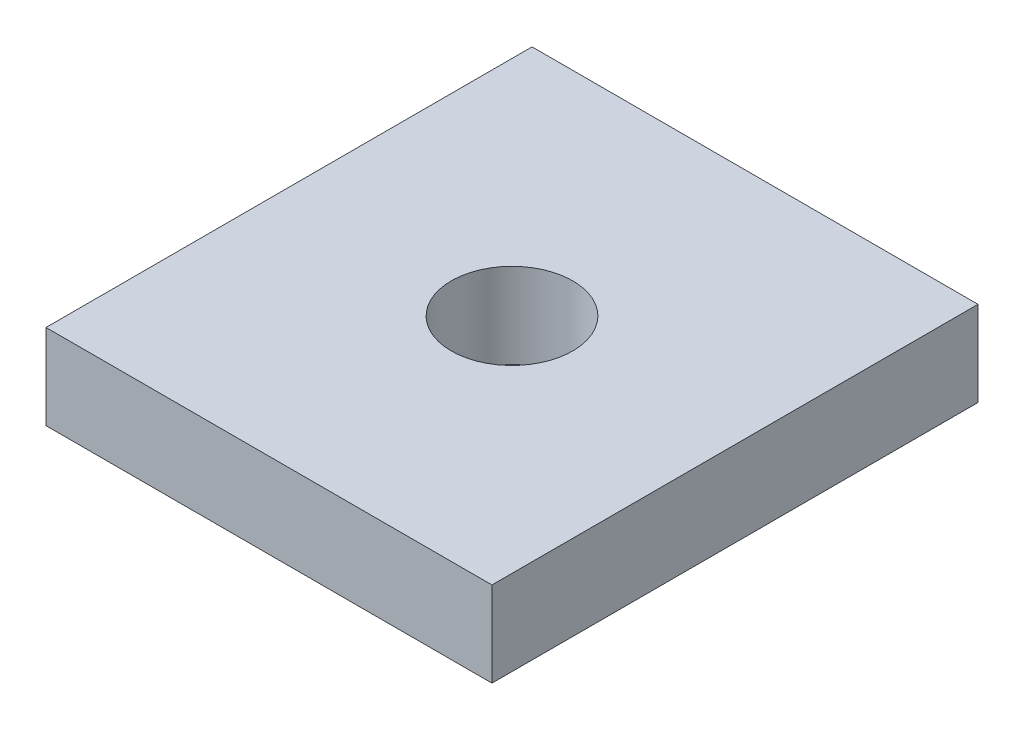
SolidWorks part; units mm, degrees
ref_plane "Alzado" through (0, 0, 0) normal (0, 0, 1) x (1, 0, 0)
ref_plane "Planta" through (0, 0, 0) normal (0, 1, 0) x (1, 0, 0)
ref_plane "Vista lateral" through (0, 0, 0) normal (1, 0, 0) x (0, 0, -1)
sketch "Croquis1" plane through (0, 0, 0) normal (0, 1, 0) x (1, 0, 0)
  line L1 (-18.35, -20) -> (18.35, -20)
  line L2 (-18.35, -20) -> (-18.35, 20)
  line L3 (-18.35, 20) -> (18.35, 20)
  line L4 (18.35, -20) -> (18.35, 20)
  line L5 (-18.35, -20) -> (18.35, 20) construction
  line L6 (-18.35, 20) -> (18.35, -20) construction
  circle A0 centre (0, 0) radius 5
  point P0 (0, 0)
  dimension "D3" = 10
  dimension "D1" = 36.7
  dimension "D2" = 40
extrude "Saliente-Extruir1" add sketch "Croquis1" along normal blind 7
